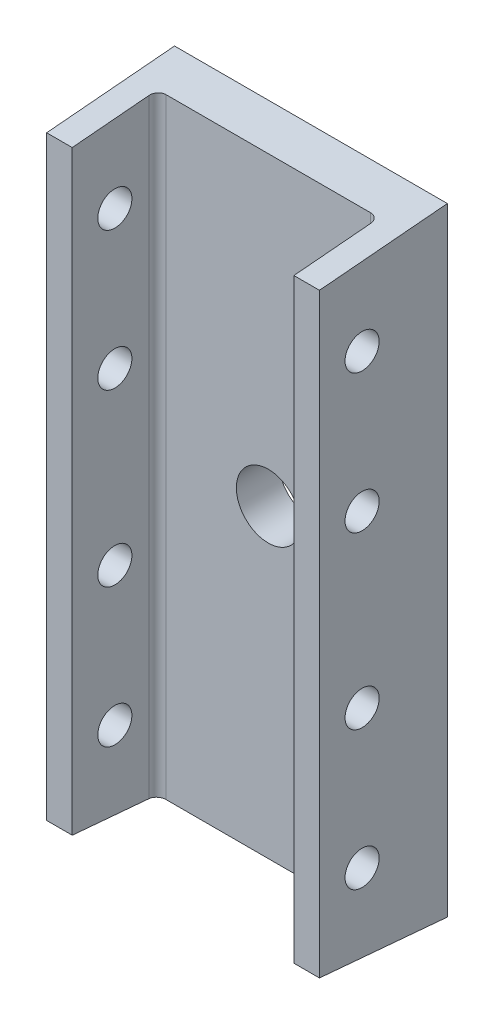
SolidWorks part; units mm, degrees
ref_plane "Front Plane" through (0, 0, 0) normal (0, 0, 1) x (1, 0, 0)
ref_plane "Top Plane" through (0, 0, 0) normal (0, 1, 0) x (1, 0, 0)
ref_plane "Right Plane" through (0, 0, 0) normal (1, 0, 0) x (0, 0, -1)
sketch "Sketch1" plane through (0, 0, 0) normal (0, 0, 1) x (1, 0, 0)
  line L1 (-16, -36.24) -> (16, -36.24)
  line L2 (-16, -36.24) -> (-16, 36.24)
  line L3 (-16, 36.24) -> (16, 36.24)
  line L4 (16, -36.24) -> (16, 36.24)
  line L5 (-16, -36.24) -> (16, 36.24) construction
  line L6 (-16, 36.24) -> (16, -36.24) construction
  circle A0 centre (0, 0) radius 3.75
  point P0 (0, 0)
  dimension "D3" = 7.5
  dimension "D1" = 32
  dimension "D2" = 72.48
extrude "Boss-Extrude1" add sketch "Sketch1" along normal blind 5
sketch "Sketch2" plane through (0, 0, 5) normal (0, 0, 1) x (1, 0, 0)
  line L0 (-16, -36.24) -> (16, -36.24) construction
  line L1 (-16, 36.24) -> (-13, 36.24)
  line L2 (-16, 36.24) -> (-16, -36.24)
  line L3 (-16, -36.24) -> (-13, -36.24)
  line L4 (-13, 36.24) -> (-13, -36.24)
  line L5 (0, 46.5577) -> (0, -47.0068) construction
  line L6 (13, 36.24) -> (13, -36.24)
  line L7 (16, -36.24) -> (13, -36.24)
  line L8 (16, 36.24) -> (16, -36.24)
  line L9 (16, 36.24) -> (13, 36.24)
  dimension "D1" = 3
extrude "Boss-Extrude2" add sketch "Sketch2" along normal blind 10
sketch "Sketch3" plane through (-13, 0, 0) normal (1, 0, 0) x (0, 0, -1)
  line L0 (-33.1752, 0) -> (25.6132, 0) construction
  circle A6 centre (-10, 26.24) radius 2
  circle A7 centre (-10, 10) radius 2
  circle A8 centre (-10, -10) radius 2
  circle A9 centre (-10, -26.24) radius 2
  dimension "D5" = 10
  dimension "D1" = 4
  dimension "D2" = 4
  dimension "D4" = 16.24
  dimension "D3" = 16.24
extrude "Cut-Extrude1" cut sketch "Sketch3" against normal through all both and the other way through all
sketch "Sketch4" plane through (-16, 0, 0) normal (-1, 0, 0) x (0, 0, 1)
  line L0 (0, 36.24) -> (15, 34.9277)
  line L1 (15, 36.24) -> (15, -36.24) construction
  line L2 (15, 34.9277) -> (15, 36.24)
  line L3 (15, 36.24) -> (0, 36.24)
  line L4 (0, 36.24) -> (0, -36.24) construction
  line L5 (-45.412, 0) -> (43.0486, 0) construction
  line L6 (15, -36.24) -> (0, -36.24)
  line L7 (15, -34.9277) -> (15, -36.24)
  line L8 (0, -36.24) -> (15, -34.9277)
  dimension "D1" = 85
extrude "Cut-Extrude2" cut sketch "Sketch4" against normal through all
fillet "Fillet1" radius 1 2 edges at (13, 0, 5) (-13, 0, 5)
